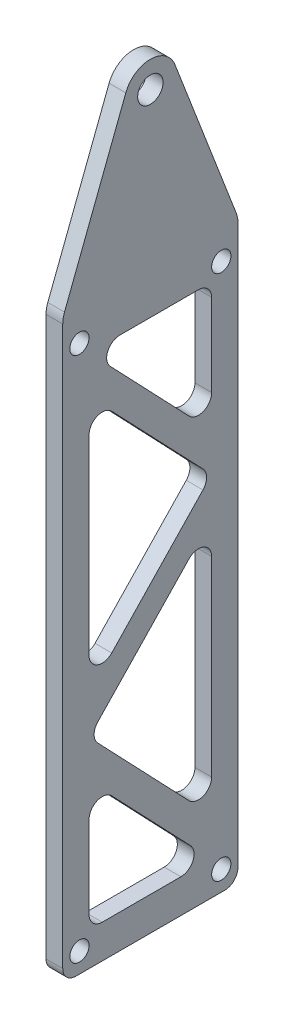
SolidWorks part; units mm, degrees
material "6061 Alloy"
ref_plane "Front Plane" through (0, 0, 0) normal (0, 0, 1) x (1, 0, 0)
ref_plane "Top Plane" through (0, 0, 0) normal (0, 1, 0) x (1, 0, 0)
ref_plane "Right Plane" through (0, 0, 0) normal (1, 0, 0) x (0, 0, -1)
sketch "Sketch1" plane through (0, 0, 0) normal (1, 0, 0) x (0, 0, -1)
  line L0 (-13.4747, 0) -> (13.4747, 0) construction
  line L1 (0, 0) -> (0, 35) construction
  line L2 (-13.4747, 0) -> (0, 35) construction
  line L3 (0, 35) -> (13.4747, 0) construction
  line L4 (13.4747, 0) -> (-13.4747, 0) construction
  line L5 (20.7574, -5) -> (-20.7574, -5)
  line L6 (-20.7574, -5) -> (0, 48.9165)
  line L7 (0, 48.9165) -> (20.7574, -5)
  line L8 (-13.4747, 0) -> (13.4747, 0) construction
  line L9 (-13.4747, 0) -> (-13.4747, -100) construction
  line L10 (13.4747, 0) -> (13.4747, -100) construction
  line L11 (-13.4747, -100) -> (13.4747, -100) construction
  line L12 (-20.7574, -5) -> (20.7574, -5)
  line L13 (-20.7574, -5) -> (-20.7574, -103.81)
  line L14 (20.7574, -5) -> (20.7574, -103.81)
  line L15 (-20.7574, -103.81) -> (20.7574, -103.81)
  circle A0 centre (-13.4747, 0) radius 1.8288
  circle A1 centre (0, 35) radius 2.413
  circle A2 centre (13.4747, 0) radius 1.8288
  circle A3 centre (-13.4747, -100) radius 1.8288
  circle A4 centre (13.4747, -100) radius 1.8288
  point P4 (0, 0)
  dimension "D3" = 3.6576
  dimension "D4" = 4.826
  dimension "D1" = 26.9494
  dimension "D5" = 100
  dimension "D6" = 3.81
  dimension "D7" = 35
  dimension "D2" = 5
extrude "Boss-Extrude1" add sketch "Sketch1" along normal blind 3.175 contours L13 L15 L14 L5 A4 A3 | L7 L6 L5 A2 A1 A0 region at (0, -54.1702, 0) region at (0, 12.8515, 0)
sketch "Sketch2" plane through (3.175, 0, 0) normal (1, 0, 0) x (0, 0, -1)
  line L3 (-11.645, -97.42) -> (-11.645, -2.5) construction
  line L4 (11.645, -97.42) -> (11.645, -2.5) construction
  line L5 (-11.645, -2.5) -> (11.645, -2.5) construction
  line L6 (-11.645, -97.42) -> (11.645, -97.42) construction
  line L7 (-20.7574, -5) -> (-20.7574, -103.81) construction
  line L9 (11.645, -2.5) -> (-11.645, -2.5)
  line L10 (-11.645, -2.5) -> (11.645, -26.8987)
  line L11 (11.645, -26.8987) -> (11.645, -2.5)
  line L12 (-11.645, -9.7413) -> (11.645, -34.14)
  line L13 (11.645, -34.14) -> (-11.645, -58.5387)
  line L14 (-11.645, -58.5387) -> (-11.645, -34.14)
  line L15 (11.645, -37.7607) -> (-11.645, -62.1593) construction
  line L16 (-11.645, -34.14) -> (-11.645, -9.7413)
  line L17 (-11.645, -73.0213) -> (-11.645, -97.42)
  line L18 (-11.645, -97.42) -> (11.645, -97.42)
  line L19 (11.645, -97.42) -> (-11.645, -73.0213)
  line L20 (11.645, -41.3813) -> (11.645, -65.78)
  line L21 (11.645, -65.78) -> (11.645, -90.1787)
  line L22 (11.645, -90.1787) -> (-11.645, -65.78)
  line L23 (-11.645, -65.78) -> (11.645, -41.3813)
  line L24 (-16.645, -1051.4901) -> (-16.645, 48948.5099) construction
  line L25 (16.645, -1047.4882) -> (16.645, 48952.5118) construction
  line L26 (-20.7574, -5) -> (-16.645, -5) construction
  line L27 (20.7574, -5) -> (16.645, -5) construction
  line L28 (-16.645, -103.81) -> (-16.645, 37.413)
  line L29 (-16.645, -103.81) -> (-20.7574, -103.81)
  line L30 (-16.645, 37.413) -> (-20.7574, 37.413)
  line L31 (-20.7574, -103.81) -> (-20.7574, 37.413)
  line L32 (-20.7574, -103.81) -> (20.7574, -103.81) construction
  line L33 (16.645, -103.81) -> (16.645, 37.413)
  line L34 (16.645, -103.81) -> (20.7574, -103.81)
  line L35 (16.645, 37.413) -> (20.7574, 37.413)
  line L36 (20.7574, -103.81) -> (20.7574, 37.413)
  circle A1 centre (13.4747, 0) radius 1.8288 construction
  circle A2 centre (0, 35) radius 2.413 construction
  circle A3 centre (13.4747, -100) radius 1.8288 construction
  point P0 (11.645, -49.96)
  point P2 (0, -97.42)
  point P28 (0, -49.96)
  dimension "D4" = 2.58
  dimension "D1" = 33.29
  dimension "D2" = 5
  dimension "D3" = 2.5
  dimension "D5" = 5
  dimension "D6" = 2.5
  dimension "D7" = 2
  dimension "D8" = 5
extrude "Cut-Extrude1" cut sketch "Sketch2" against normal through all
fillet "Fillet1" radius 2.5 14 edges at (1.5875, -97.42, -11.645) (1.5875, -90.1787, -11.645) (1.5875, -41.3813, -11.645) (1.5875, -73.0213, 11.645) (1.5875, -97.42, 11.645) (1.5875, -65.78, 11.645) (1.5875, -58.5387, 11.645) (1.5875, -34.14, -11.645) (1.5875, -9.7413, 11.645) (1.5875, -2.5, 11.645) (1.5875, -26.8987, -11.645) (1.5875, -2.5, -11.645) (1.5875, -103.81, 16.645) (1.5875, -103.81, -16.645)
fillet "Fillet2" radius 5 3 edges at (1.5875, 48.9165, 0) (1.5875, 5.6818, 16.645) (1.5875, 5.6818, -16.645)
